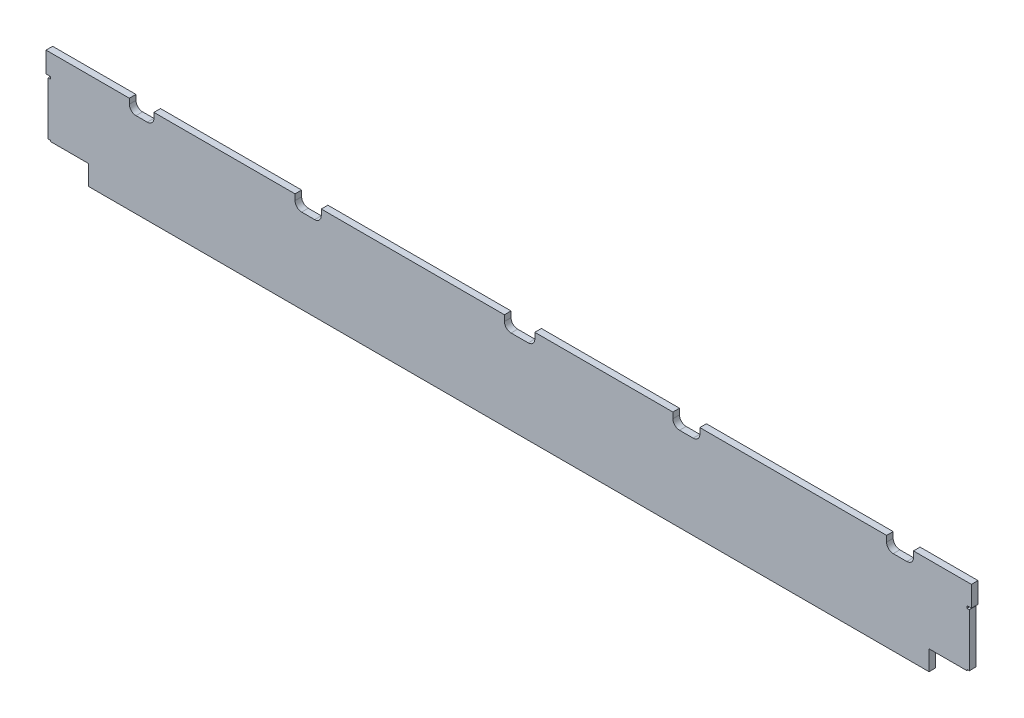
SolidWorks part; units mm, degrees
material "PP Film"
ref_plane "X-Y Datum" through (0, 0, 0) normal (0, 0, 1) x (1, 0, 0)
ref_plane "X-Z Datum" through (0, 0, 0) normal (0, 1, 0) x (1, 0, 0)
ref_plane "Y-Z Datum" through (0, 0, 0) normal (1, 0, 0) x (0, 0, -1)
sketch "Sketch2" plane through (0, 0, 0) normal (0, 0, 1) x (1, 0, 0)
  line L0 (-174.4992, -157.216) -> (269.7668, -157.216)
  line L41 (249.4468, -194.181) -> (267.6238, -194.181)
  line L42 (267.6238, -194.181) -> (267.6238, -193.665)
  line L43 (267.6238, -193.665) -> (268.7668, -193.665)
  line L44 (268.7668, -193.665) -> (268.7668, -168.265)
  line L45 (268.7668, -168.265) -> (267.6238, -168.265)
  line L46 (267.6238, -168.265) -> (267.6238, -167.122)
  line L47 (267.6238, -167.122) -> (269.7668, -167.122)
  line L48 (269.7668, -167.122) -> (269.7668, -157.216)
  line L50 (-174.4992, -157.216) -> (-174.4992, -167.122)
  line L51 (-174.4992, -167.122) -> (-172.3562, -167.122)
  line L52 (-172.3562, -167.122) -> (-172.3562, -168.265)
  line L53 (-172.3562, -168.265) -> (-173.4992, -168.265)
  line L54 (-173.4992, -168.265) -> (-173.4992, -193.665)
  line L55 (-173.4992, -193.665) -> (-172.3562, -193.665)
  line L56 (-172.3562, -193.665) -> (-172.3562, -194.181)
  line L57 (-172.3562, -194.181) -> (-154.1792, -194.181)
  line L58 (-154.1792, -194.181) -> (-154.1792, -203.714)
  line L59 (-154.1792, -203.714) -> (249.4468, -203.714)
  line L196 (249.4468, -203.714) -> (249.4468, -194.181)
  line L613 (-125.8659, -162.8707) -> (-131.3072, -162.8707)
  line L615 (-134.4822, -159.6957) -> (-134.4822, -157.216)
  line L617 (241.9429, -157.216) -> (241.9429, -160.0289)
  line L619 (238.7679, -163.2039) -> (232.2288, -163.2039)
  line L621 (229.0538, -160.0289) -> (229.0538, -157.216)
  line L623 (229.0538, -157.216) -> (139.3917, -157.216)
  line L625 (139.3917, -157.216) -> (139.3917, -160.0289)
  line L627 (136.2167, -163.2039) -> (129.6343, -163.2039)
  line L629 (126.4593, -160.0289) -> (126.4593, -157.216)
  line L631 (126.4593, -157.216) -> (60.1739, -157.216)
  line L633 (60.1739, -157.216) -> (60.1739, -160.0289)
  line L635 (56.9989, -163.2039) -> (48.7597, -163.2039)
  line L637 (45.5847, -160.0289) -> (45.5847, -157.216)
  line L639 (45.5847, -157.216) -> (-42.3503, -157.216)
  line L641 (-42.3503, -157.216) -> (-42.3503, -160.0289)
  line L643 (-45.5253, -163.2039) -> (-51.766, -163.2039)
  line L645 (-54.941, -160.0289) -> (-54.941, -157.216)
  line L647 (-54.941, -157.216) -> (-122.6909, -157.216)
  line L649 (-122.6909, -157.216) -> (-122.6909, -159.6957)
  arc A21 (-125.8659, -162.8707) -> (-122.6909, -159.6957) centre (-125.8659, -159.6957) ccw
  arc A23 (-134.4822, -159.6957) -> (-131.3072, -162.8707) centre (-131.3072, -159.6957) ccw
  arc A25 (238.7679, -163.2039) -> (241.9429, -160.0289) centre (238.7679, -160.0289) ccw
  arc A27 (229.0538, -160.0289) -> (232.2288, -163.2039) centre (232.2288, -160.0289) ccw
  arc A29 (136.2167, -163.2039) -> (139.3917, -160.0289) centre (136.2167, -160.0289) ccw
  arc A31 (126.4593, -160.0289) -> (129.6343, -163.2039) centre (129.6343, -160.0289) ccw
  arc A33 (56.9989, -163.2039) -> (60.1739, -160.0289) centre (56.9989, -160.0289) ccw
  arc A35 (45.5847, -160.0289) -> (48.7597, -163.2039) centre (48.7597, -160.0289) ccw
  arc A37 (-45.5253, -163.2039) -> (-42.3503, -160.0289) centre (-45.5253, -160.0289) ccw
  arc A39 (-54.941, -160.0289) -> (-51.766, -163.2039) centre (-51.766, -160.0289) ccw
extrude "Boss-Extrude1" add sketch "Sketch2" along normal blind 3.175 contours L58 L59 L196 L41 L42 L43 L44 L45 L46 L47 L48 L50 L51 L52 L53 L54 L55 L56 L57 region at (47.5065, -180.4774, 0)
